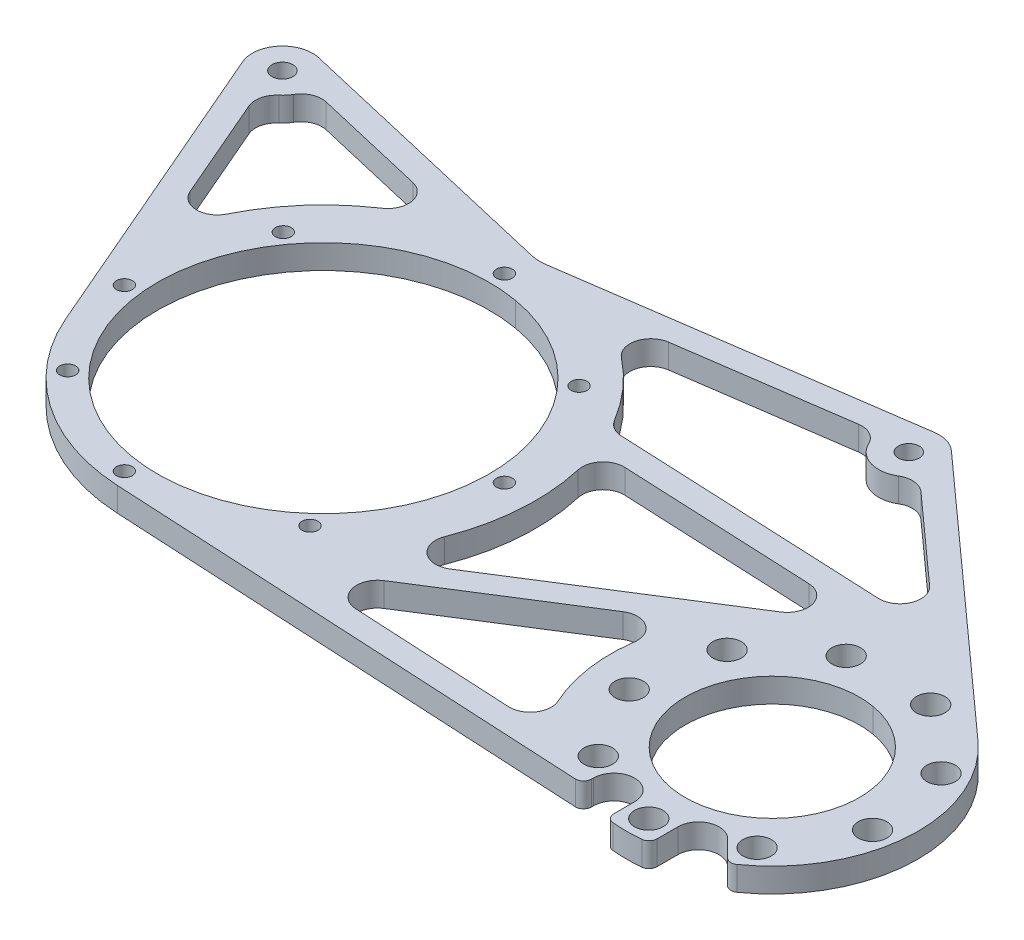
SolidWorks part; units mm, degrees
material "6061-T6 (SS)"
ref_plane "X-Y Datum" through (0, 0, 0) normal (0, 0, 1) x (1, 0, 0)
ref_plane "X-Z Datum" through (0, 0, 0) normal (0, 1, 0) x (1, 0, 0)
ref_plane "Y-Z Datum" through (0, 0, 0) normal (1, 0, 0) x (0, 0, -1)
sketch "Sketch2" plane through (0, 31.3819, 0) normal (0, 1, 0) x (1, 0, 0)
  line L0 (-693.7583, -176.702) -> (-693.7583, -183.2747) construction
  line L1 (-680.0808, -183.2747) -> (-680.0808, -176.702) construction
  line L2 (-668.9846, -172.1058) -> (-663.7197, -177.3707) construction
  line L3 (-693.7583, -176.702) -> (-693.7583, -183.2747)
  line L4 (-680.0808, -183.2747) -> (-680.0808, -176.702)
  line L5 (-668.9846, -172.1058) -> (-663.7197, -177.3707)
  line L6 (-966.641, -0.354) -> (-738.041, -0.354)
  line L7 (-727.7656, -5.5904) -> (-649.7224, -113.0358)
  line L9 (-977.8288, -19.0644) -> (-913.2312, -139.3061)
  line L10 (-706.7583, -177.279) -> (-706.7583, -176.702) construction
  line L11 (-706.7583, -177.279) -> (-706.7583, -176.702)
  line L12 (-861.9259, -171.8334) -> (-709.2983, -179.819)
  line L13 (-858.691, -110.0055) -> (-686.9195, -140.054) construction
  line L14 (-972.26, -24.9963) -> (-955.4664, -39.59) construction
  line L15 (-941.4162, -26.937) -> (-954.1775, -8.712) construction
  line L16 (-751.1929, -14.159) -> (-755.4346, -35.9995) construction
  line L17 (-737.4517, -41.8408) -> (-728.049, -21.6768) construction
  line L18 (-972.26, -24.9963) -> (-955.4664, -39.59)
  line L19 (-941.4162, -26.937) -> (-954.1775, -8.712)
  line L20 (-751.1929, -14.159) -> (-755.4346, -35.9995)
  line L21 (-737.4517, -41.8408) -> (-728.049, -21.6768)
  line L22 (-949.2186, -22.8753) -> (-746.0843, -28.2904)
  line L23 (-739.7146, -30.7335) -> (-656.1751, -105.8723)
  line L24 (-957.9647, -36.1729) -> (-915.5404, -134.527)
  arc A0 (-710.607, -179.4559) -> (-706.7583, -177.279) centre (-709.2983, -177.279) ccw construction
  arc A1 (-693.7583, -176.702) -> (-706.7583, -176.702) centre (-700.2583, -176.702) ccw construction
  arc A2 (-693.7583, -183.2747) -> (-691.4697, -185.8023) centre (-691.2183, -183.2747) ccw construction
  arc A3 (-691.4697, -185.8023) -> (-682.3694, -185.8023) centre (-686.9195, -140.054) ccw construction
  arc A4 (-682.3694, -185.8023) -> (-680.0808, -183.2747) centre (-682.6208, -183.2747) ccw construction
  arc A5 (-668.9846, -172.1058) -> (-680.0808, -176.702) centre (-673.5808, -176.702) ccw construction
  arc A6 (-663.7197, -177.3707) -> (-660.4619, -177.6519) centre (-661.9236, -175.5746) ccw construction
  arc A7 (-660.4619, -177.6519) -> (-710.607, -179.4559) centre (-686.9195, -140.054) ccw construction
  circle A8 centre (-858.691, -110.0055) radius 52.3875 construction
  circle A9 centre (-858.691, -110.0055) radius 61.9125 construction
  circle A10 centre (-738.041, -13.054) radius 12.7 construction
  circle A11 centre (-966.641, -13.054) radius 12.7 construction
  arc A12 (-710.607, -179.4559) -> (-706.7583, -177.279) centre (-709.2983, -177.279) ccw
  arc A13 (-693.7583, -176.702) -> (-706.7583, -176.702) centre (-700.2583, -176.702) ccw
  arc A14 (-693.7583, -183.2747) -> (-691.4697, -185.8023) centre (-691.2183, -183.2747) ccw
  arc A15 (-691.4697, -185.8023) -> (-682.3694, -185.8023) centre (-686.9195, -140.054) ccw
  arc A16 (-682.3694, -185.8023) -> (-680.0808, -183.2747) centre (-682.6208, -183.2747) ccw
  arc A17 (-668.9846, -172.1058) -> (-680.0808, -176.702) centre (-673.5808, -176.702) ccw
  arc A18 (-663.7197, -177.3707) -> (-660.4619, -177.6519) centre (-661.9236, -175.5746) ccw
  arc A19 (-660.4619, -177.6519) -> (-710.607, -179.4559) centre (-686.9195, -140.054) ccw
  circle A20 centre (-858.691, -110.0055) radius 52.3875
  circle A21 centre (-858.691, -110.0055) radius 61.9125
  circle A22 centre (-738.041, -13.054) radius 12.7
  circle A23 centre (-966.641, -13.054) radius 12.7
  circle A24 centre (-901.1618, -148.2463) radius 2.5 construction
  circle A25 centre (-915.528, -115.9793) radius 2.5 construction
  circle A26 centre (-904.9264, -76.4135) radius 2.5 construction
  circle A27 centre (-858.691, -52.8555) radius 2.5 construction
  circle A28 centre (-816.2203, -71.7646) radius 2.5 construction
  circle A29 centre (-801.541, -110.0055) radius 2.5 construction
  circle A30 centre (-820.4502, -152.4762) radius 2.5 construction
  circle A31 centre (-864.6648, -166.8424) radius 2.5 construction
  circle A32 centre (-901.1618, -148.2463) radius 2.5
  circle A33 centre (-915.528, -115.9793) radius 2.5
  circle A34 centre (-904.9264, -76.4135) radius 2.5
  circle A35 centre (-858.691, -52.8555) radius 2.5
  circle A36 centre (-816.2203, -71.7646) radius 2.5
  circle A37 centre (-801.541, -110.0055) radius 2.5
  circle A38 centre (-820.4502, -152.4762) radius 2.5
  circle A39 centre (-864.6648, -166.8424) radius 2.5
  circle A40 centre (-686.9195, -140.054) radius 27.4955 construction
  circle A41 centre (-686.9195, -140.054) radius 27.4955
  circle A42 centre (-711.9883, -169.9297) radius 4.5 construction
  circle A43 centre (-725.3271, -146.8263) radius 4.5 construction
  circle A44 centre (-720.6945, -120.554) radius 4.5 construction
  circle A45 centre (-700.2583, -103.406) radius 4.5 construction
  circle A46 centre (-673.5808, -103.406) radius 4.5 construction
  circle A47 centre (-653.1446, -120.554) radius 4.5 construction
  circle A48 centre (-648.512, -146.8263) radius 4.5 construction
  circle A49 centre (-661.8508, -169.9297) radius 4.5 construction
  circle A50 centre (-686.9195, -179.054) radius 4.5 construction
  circle A51 centre (-711.9883, -169.9297) radius 4.5
  circle A52 centre (-725.3271, -146.8263) radius 4.5
  circle A53 centre (-720.6945, -120.554) radius 4.5
  circle A54 centre (-700.2583, -103.406) radius 4.5
  circle A55 centre (-673.5808, -103.406) radius 4.5
  circle A56 centre (-653.1446, -120.554) radius 4.5
  circle A57 centre (-648.512, -146.8263) radius 4.5
  circle A58 centre (-661.8508, -169.9297) radius 4.5
  circle A59 centre (-686.9195, -179.054) radius 4.5
  circle A60 centre (-966.641, -13.054) radius 3.3
  circle A61 centre (-738.041, -13.054) radius 3.3
  arc A62 (-955.4664, -39.59) -> (-941.4162, -26.937) centre (-949.2186, -32.4003) ccw construction
  arc A63 (-749.3237, -37.1863) -> (-742.8448, -38.4445) centre (-746.0843, -37.8154) ccw construction
  arc A64 (-742.8448, -38.4445) -> (-749.3237, -37.1863) centre (-746.0843, -37.8154) ccw construction
  arc A65 (-755.4346, -35.9995) -> (-737.4517, -41.8408) centre (-746.0843, -37.8154) ccw construction
  arc A66 (-955.4664, -39.59) -> (-941.4162, -26.937) centre (-949.2186, -32.4003) ccw
  arc A67 (-749.3237, -37.1863) -> (-742.8448, -38.4445) centre (-746.0843, -37.8154) ccw
  arc A68 (-742.8448, -38.4445) -> (-749.3237, -37.1863) centre (-746.0843, -37.8154) ccw
  arc A69 (-755.4346, -35.9995) -> (-737.4517, -41.8408) centre (-746.0843, -37.8154) ccw
  circle A70 centre (-949.2186, -32.4003) radius 3.3
  circle A71 centre (-949.2186, -32.4003) radius 9.525
  circle A72 centre (-746.0843, -37.8154) radius 9.525
  point P94 (-949.2186, -32.4003)
  dimension "D1" = 6.6
  dimension "D2" = 6.6
  dimension "D3" = 6.6
extrude "Boss-Extrude1" add sketch "Sketch2" along normal blind 7.62 contours A21 A39 A38 A37 A36 A35 A34 A33 A32 A20 | A18 A19 A12 L11 A13 L3 A14 A15 A16 L4 A17 L5 A59 A58 A57 A56 A55 A54 A53 A52 A51 A41 | L13 A21 L12 A12 A19 | A21 L13 A19 L23 L21 A69 L20 L22 L19 A66 L18 L24 | A69 A72 A68 A67 | A72 L22 L20 | A72 L21 L23 | A71 L24 L18 | A71 L19 L22 | A71 A66 L22 A70 region at (-700.2583, 31.3819, 168.9016) region at (-773.051, 31.3819, 154.3682) region at (-890.9045, 31.3819, 160.8157) region at (-806.8861, 31.3819, 67.2042) region at (-956.9478, 31.3819, 38.0512) region at (-736.2382, 31.3819, 35.8095) region at (-956.6903, 31.3819, 37.8629) region at (-748.9437, 31.3819, 46.6182) region at (-752.4763, 31.3819, 29.8585) region at (-944.5842, 31.3819, 23.8004)
sketch "Sketch3" plane through (0, 31.3819, 0) normal (0, -1, 0) x (1, 0, 0)
  line L1 (-949.2186, 22.8753) -> (-746.0843, 28.2904) construction
  line L5 (-861.9259, 171.8334) -> (-709.2983, 179.819) construction
  line L6 (-977.8288, 19.0644) -> (-913.2312, 139.3061) construction
  line L7 (-727.7656, 5.5904) -> (-649.7224, 113.0358) construction
  line L13 (-751.1929, 14.159) -> (-755.4346, 35.9995) construction
  line L16 (-966.641, 0.354) -> (-738.041, 0.354) construction
  line L19 (-663.7197, 177.3707) -> (-668.9846, 172.1058)
  line L20 (-680.0808, 176.702) -> (-680.0808, 183.2747)
  line L21 (-693.7583, 183.2747) -> (-693.7583, 176.702)
  line L22 (-706.7583, 176.702) -> (-706.7583, 177.279)
  line L23 (-663.7197, 177.3707) -> (-668.9846, 172.1058)
  line L24 (-680.0808, 176.702) -> (-680.0808, 183.2747)
  line L25 (-693.7583, 183.2747) -> (-693.7583, 176.702)
  line L26 (-706.7583, 176.702) -> (-706.7583, 177.279)
  line L28 (-861.9259, 171.8334) -> (-709.2983, 179.819)
  line L29 (-977.8288, 19.0644) -> (-913.2312, 139.3061)
  line L30 (-727.7656, 5.5904) -> (-649.7224, 113.0358)
  line L31 (-966.641, 0.354) -> (-738.041, 0.354)
  line L34 (-737.4517, 41.8408) -> (-728.049, 21.6768) construction
  line L35 (-972.26, 24.9963) -> (-955.4664, 39.59) construction
  line L36 (-947.0539, 23.1246) -> (-856.9722, 44.1471)
  line L37 (-856.9722, 44.1471) -> (-747.4408, 28.3875)
  line L44 (-941.4162, 26.937) -> (-954.1775, 8.712) construction
  line L45 (-957.9647, 36.1729) -> (-915.5404, 134.527) construction
  line L46 (-739.7146, 30.7335) -> (-656.1751, 105.8723) construction
  line L47 (-861.9259, 171.8334) -> (-709.2983, 179.819)
  line L48 (-977.8288, 19.0644) -> (-913.2312, 139.3061)
  line L49 (-727.7656, 5.5904) -> (-649.7224, 113.0358)
  line L50 (-966.641, 0.354) -> (-738.041, 0.354)
  line L51 (-949.2186, 22.8753) -> (-746.0843, 28.2904)
  line L52 (-751.1929, 14.159) -> (-755.4346, 35.9995)
  line L53 (-737.4517, 41.8408) -> (-728.049, 21.6768)
  line L54 (-972.26, 24.9963) -> (-955.4664, 39.59)
  line L55 (-941.4162, 26.937) -> (-954.1775, 8.712)
  line L56 (-957.9647, 36.1729) -> (-915.5404, 134.527)
  line L57 (-739.7146, 30.7335) -> (-656.1751, 105.8723)
  arc A1 (-737.4517, 41.8408) -> (-755.4346, 35.9995) centre (-746.0843, 37.8154) ccw construction
  circle A3 centre (-966.641, 13.054) radius 12.7
  circle A5 centre (-966.641, 13.054) radius 12.7
  circle A7 centre (-738.041, 13.054) radius 12.7
  circle A9 centre (-738.041, 13.054) radius 12.7
  circle A11 centre (-858.691, 110.0055) radius 61.9125
  circle A13 centre (-858.691, 110.0055) radius 61.9125
  circle A15 centre (-858.691, 110.0055) radius 52.3875
  circle A17 centre (-858.691, 110.0055) radius 52.3875
  circle A19 centre (-686.9195, 140.054) radius 27.4955
  circle A21 centre (-686.9195, 140.054) radius 27.4955
  circle A23 centre (-864.6648, 166.8424) radius 2.5
  circle A25 centre (-864.6648, 166.8424) radius 2.5
  circle A27 centre (-820.4502, 152.4762) radius 2.5
  circle A29 centre (-820.4502, 152.4762) radius 2.5
  circle A31 centre (-801.541, 110.0055) radius 2.5
  circle A33 centre (-801.541, 110.0055) radius 2.5
  circle A35 centre (-816.2203, 71.7646) radius 2.5
  circle A37 centre (-816.2203, 71.7646) radius 2.5
  circle A39 centre (-858.691, 52.8555) radius 2.5
  circle A41 centre (-858.691, 52.8555) radius 2.5
  circle A43 centre (-904.9264, 76.4135) radius 2.5
  circle A46 centre (-904.9264, 76.4135) radius 2.5
  circle A47 centre (-915.528, 115.9793) radius 2.5
  circle A48 centre (-915.528, 115.9793) radius 2.5
  circle A49 centre (-901.1618, 148.2463) radius 2.5
  circle A50 centre (-901.1618, 148.2463) radius 2.5
  circle A51 centre (-720.6945, 120.554) radius 4.5
  circle A52 centre (-720.6945, 120.554) radius 4.5
  circle A68 centre (-725.3271, 146.8263) radius 4.5
  circle A69 centre (-725.3271, 146.8263) radius 4.5
  circle A70 centre (-711.9883, 169.9297) radius 4.5
  circle A71 centre (-711.9883, 169.9297) radius 4.5
  circle A72 centre (-738.041, 13.054) radius 3.3
  circle A73 centre (-738.041, 13.054) radius 3.3
  circle A74 centre (-966.641, 13.054) radius 3.3
  circle A75 centre (-966.641, 13.054) radius 3.3
  circle A76 centre (-686.9195, 179.054) radius 4.5
  circle A77 centre (-686.9195, 179.054) radius 4.5
  circle A78 centre (-661.8508, 169.9297) radius 4.5
  circle A79 centre (-661.8508, 169.9297) radius 4.5
  circle A80 centre (-648.512, 146.8263) radius 4.5
  circle A81 centre (-648.512, 146.8263) radius 4.5
  circle A82 centre (-653.1446, 120.554) radius 4.5
  circle A83 centre (-653.1446, 120.554) radius 4.5
  circle A84 centre (-673.5808, 103.406) radius 4.5
  circle A85 centre (-673.5808, 103.406) radius 4.5
  circle A86 centre (-700.2583, 103.406) radius 4.5
  circle A87 centre (-700.2583, 103.406) radius 4.5
  arc A95 (-710.607, 179.4559) -> (-660.4619, 177.6519) centre (-686.9195, 140.054) ccw
  arc A96 (-660.4619, 177.6519) -> (-663.7197, 177.3707) centre (-661.9236, 175.5746) ccw
  arc A97 (-680.0808, 176.702) -> (-668.9846, 172.1058) centre (-673.5808, 176.702) ccw
  arc A98 (-680.0808, 183.2747) -> (-682.3694, 185.8023) centre (-682.6208, 183.2747) ccw
  arc A99 (-682.3694, 185.8023) -> (-691.4697, 185.8023) centre (-686.9195, 140.054) ccw
  arc A100 (-691.4697, 185.8023) -> (-693.7583, 183.2747) centre (-691.2183, 183.2747) ccw
  arc A101 (-706.7583, 176.702) -> (-693.7583, 176.702) centre (-700.2583, 176.702) ccw
  arc A102 (-706.7583, 177.279) -> (-710.607, 179.4559) centre (-709.2983, 177.279) ccw
  arc A103 (-710.607, 179.4559) -> (-660.4619, 177.6519) centre (-686.9195, 140.054) ccw
  arc A104 (-660.4619, 177.6519) -> (-663.7197, 177.3707) centre (-661.9236, 175.5746) ccw
  arc A105 (-680.0808, 176.702) -> (-668.9846, 172.1058) centre (-673.5808, 176.702) ccw
  arc A106 (-680.0808, 183.2747) -> (-682.3694, 185.8023) centre (-682.6208, 183.2747) ccw
  arc A107 (-682.3694, 185.8023) -> (-691.4697, 185.8023) centre (-686.9195, 140.054) ccw
  arc A108 (-691.4697, 185.8023) -> (-693.7583, 183.2747) centre (-691.2183, 183.2747) ccw
  arc A109 (-706.7583, 176.702) -> (-693.7583, 176.702) centre (-700.2583, 176.702) ccw
  arc A110 (-706.7583, 177.279) -> (-710.607, 179.4559) centre (-709.2983, 177.279) ccw
  circle A152 centre (-746.0843, 37.8154) radius 9.525
  circle A153 centre (-746.0843, 37.8154) radius 9.525
  circle A154 centre (-949.2186, 32.4003) radius 9.525
  circle A155 centre (-949.2186, 32.4003) radius 9.525
  circle A156 centre (-949.2186, 32.4003) radius 3.3
  circle A157 centre (-949.2186, 32.4003) radius 3.3
  arc A158 (-941.4162, 26.937) -> (-955.4664, 39.59) centre (-949.2186, 32.4003) ccw construction
  arc A159 (-742.8448, 38.4445) -> (-749.3237, 37.1863) centre (-746.0843, 37.8154) ccw
  arc A160 (-749.3237, 37.1863) -> (-742.8448, 38.4445) centre (-746.0843, 37.8154) ccw
  arc A161 (-742.8448, 38.4445) -> (-749.3237, 37.1863) centre (-746.0843, 37.8154) ccw
  arc A162 (-749.3237, 37.1863) -> (-742.8448, 38.4445) centre (-746.0843, 37.8154) ccw
  arc A163 (-737.4517, 41.8408) -> (-755.4346, 35.9995) centre (-746.0843, 37.8154) ccw
  arc A164 (-941.4162, 26.937) -> (-955.4664, 39.59) centre (-949.2186, 32.4003) ccw
  dimension "D24" = 0
  dimension "D25" = 0
  dimension "D26" = 90.0818
  dimension "D27" = 21.0225
  dimension "D1" = 0
  dimension "D2" = 0
  dimension "D3" = 0
  dimension "D4" = 0
  dimension "D5" = 0
  dimension "D6" = 0
  dimension "D7" = 0
  dimension "D8" = 0
  dimension "D9" = 0
  dimension "D10" = 0
  dimension "D11" = 0
  dimension "D12" = 0
  dimension "D13" = 0
  dimension "D14" = 0
  dimension "D15" = 0
  dimension "D16" = 0
  dimension "D17" = 0
  dimension "D18" = 0
  dimension "D19" = 0
  dimension "D20" = 0
  dimension "D21" = 0
  dimension "D22" = 0
  dimension "D23" = 0
  dimension "D52" = 0
  dimension "D53" = 0
  dimension "D54" = 0
  dimension "D55" = 0
ref_point "Point1"
ref_point "Point2"
ref_plane "Plane1" through (-858.691, 31.3819, 110.0055) normal (0.985, 0, 0.1723) x (0.1723, 0, -0.985)
ref_plane "Plane2" through (-686.9195, 31.3819, 140.054) normal (-0.985, 0, -0.1723) x (-0.1723, 0, 0.985)
split line "Split Line1"
split line "Split Line2"
ref_axis "Axis1" through (-858.691, 39.0019, 110.0055) along (0, -1, 0)
ref_axis "Axis2" through (-686.9195, 39.0019, 140.054) along (0, -1, 0)
extrude "Cut-Extrude1" cut sketch "Sketch3" against normal through all contours L36 L55 L51 L52 L37 | A155 L51 L55 L36 | A153 L37 L52 L51 region at (-751.5495, 31.3819, 28.5688) region at (-850.6911, 31.3819, 31.7926) region at (-945.2616, 31.3819, 23.2848)
fillet "Fillet2" radius 12.7 1 edges at (-856.9722, 35.1919, 44.1471)
sketch "Sketch4" plane through (0, 31.3819, 0) normal (0, -1, 0) x (1, 0, 0)
  line L0 (-861.9259, 171.8334) -> (-709.2983, 179.819) construction
  line L1 (-727.7656, 5.5904) -> (-649.7224, 113.0358) construction
  line L2 (-977.8288, 19.0644) -> (-913.2312, 139.3061) construction
  line L4 (-706.7583, 176.702) -> (-706.7583, 177.279)
  line L5 (-663.7197, 177.3707) -> (-668.9846, 172.1058)
  line L6 (-680.0808, 176.702) -> (-680.0808, 183.2747)
  line L7 (-693.7583, 183.2747) -> (-693.7583, 176.702)
  line L8 (-706.7583, 176.702) -> (-706.7583, 177.279)
  line L9 (-663.7197, 177.3707) -> (-668.9846, 172.1058)
  line L10 (-680.0808, 176.702) -> (-680.0808, 183.2747)
  line L11 (-693.7583, 183.2747) -> (-693.7583, 176.702)
  line L13 (-966.641, 0.354) -> (-738.041, 0.354) construction
  line L14 (-861.9259, 171.8334) -> (-709.2983, 179.819)
  line L15 (-727.7656, 5.5904) -> (-649.7224, 113.0358)
  line L16 (-977.8288, 19.0644) -> (-913.2312, 139.3061)
  line L17 (-861.9259, 171.8334) -> (-709.2983, 179.819) construction
  line L19 (-966.641, 0.354) -> (-738.041, 0.354)
  line L20 (-924.088, 95.4716) -> (-952.4637, 29.6868)
  line L21 (-952.4637, 29.6868) -> (-880.185, 46.5546)
  line L22 (-727.338, 171.2447) -> (-811.2904, 166.8523)
  line L23 (-811.2904, 166.8523) -> (-732.4764, 117.0088)
  line L24 (-812.7344, 158.7495) -> (-704.8294, 90.5083)
  line L25 (-704.8294, 90.5083) -> (-795.9976, 86.3933)
  line L26 (-832.536, 48.3296) -> (-755.593, 37.2589)
  line L27 (-799.5123, 78.6069) -> (-692.5141, 83.4364)
  line L28 (-692.5141, 83.4364) -> (-737.8716, 42.64)
  line L29 (-977.8288, 19.0644) -> (-913.2312, 139.3061) construction
  line L30 (-727.7656, 5.5904) -> (-649.7224, 113.0358) construction
  line L31 (-966.641, 0.354) -> (-738.041, 0.354) construction
  line L32 (-663.7197, 177.3707) -> (-668.9846, 172.1058)
  line L33 (-680.0808, 176.702) -> (-680.0808, 183.2747)
  line L34 (-693.7583, 183.2747) -> (-693.7583, 176.702)
  line L35 (-706.7583, 176.702) -> (-706.7583, 177.279)
  line L36 (-663.7197, 177.3707) -> (-668.9846, 172.1058)
  line L37 (-680.0808, 176.702) -> (-680.0808, 183.2747)
  line L38 (-693.7583, 183.2747) -> (-693.7583, 176.702)
  line L39 (-706.7583, 176.702) -> (-706.7583, 177.279)
  line L40 (-949.2186, 22.8753) -> (-746.0843, 28.2904) construction
  line L41 (-751.1929, 14.159) -> (-755.4346, 35.9995) construction
  line L42 (-737.4517, 41.8408) -> (-728.049, 21.6768) construction
  line L43 (-972.26, 24.9963) -> (-955.4664, 39.59) construction
  line L44 (-941.4162, 26.937) -> (-954.1775, 8.712) construction
  line L45 (-957.9647, 36.1729) -> (-915.5404, 134.527) construction
  line L46 (-739.7146, 30.7335) -> (-656.1751, 105.8723) construction
  line L47 (-861.9259, 171.8334) -> (-709.2983, 179.819)
  line L48 (-977.8288, 19.0644) -> (-913.2312, 139.3061)
  line L49 (-727.7656, 5.5904) -> (-649.7224, 113.0358)
  line L50 (-966.641, 0.354) -> (-738.041, 0.354)
  line L51 (-949.2186, 22.8753) -> (-746.0843, 28.2904)
  line L52 (-751.1929, 14.159) -> (-755.4346, 35.9995)
  line L53 (-737.4517, 41.8408) -> (-728.049, 21.6768)
  line L54 (-972.26, 24.9963) -> (-955.4664, 39.59)
  line L55 (-941.4162, 26.937) -> (-954.1775, 8.712)
  line L56 (-957.9647, 36.1729) -> (-915.5404, 134.527)
  line L57 (-739.7146, 30.7335) -> (-656.1751, 105.8723)
  line L58 (-947.0539, 23.1246) -> (-859.3005, 43.6037) construction
  line L60 (-854.6056, 43.8066) -> (-747.4408, 28.3875) construction
  circle A1 centre (-858.691, 110.0055) radius 52.3875
  circle A2 centre (-858.691, 110.0055) radius 52.3875
  circle A3 centre (-858.691, 110.0055) radius 61.9125
  circle A4 centre (-858.691, 110.0055) radius 61.9125
  circle A5 centre (-738.041, 13.054) radius 12.7
  circle A6 centre (-738.041, 13.054) radius 12.7
  circle A7 centre (-966.641, 13.054) radius 12.7
  circle A8 centre (-966.641, 13.054) radius 12.7
  circle A9 centre (-858.691, 52.8555) radius 2.5
  circle A10 centre (-858.691, 52.8555) radius 2.5
  circle A11 centre (-816.2203, 71.7646) radius 2.5
  circle A12 centre (-816.2203, 71.7646) radius 2.5
  circle A13 centre (-801.541, 110.0055) radius 2.5
  circle A14 centre (-801.541, 110.0055) radius 2.5
  circle A15 centre (-820.4502, 152.4762) radius 2.5
  circle A16 centre (-820.4502, 152.4762) radius 2.5
  circle A17 centre (-864.6648, 166.8424) radius 2.5
  circle A18 centre (-864.6648, 166.8424) radius 2.5
  circle A19 centre (-686.9195, 140.054) radius 27.4955
  circle A20 centre (-686.9195, 140.054) radius 27.4955
  circle A21 centre (-725.3271, 146.8263) radius 4.5
  circle A22 centre (-725.3271, 146.8263) radius 4.5
  circle A23 centre (-720.6945, 120.554) radius 4.5
  circle A24 centre (-720.6945, 120.554) radius 4.5
  circle A25 centre (-901.1618, 148.2463) radius 2.5
  circle A26 centre (-901.1618, 148.2463) radius 2.5
  circle A27 centre (-915.528, 115.9793) radius 2.5
  circle A28 centre (-915.528, 115.9793) radius 2.5
  circle A29 centre (-904.9264, 76.4135) radius 2.5
  circle A30 centre (-904.9264, 76.4135) radius 2.5
  circle A31 centre (-661.8508, 169.9297) radius 4.5
  circle A32 centre (-661.8508, 169.9297) radius 4.5
  circle A33 centre (-686.9195, 179.054) radius 4.5
  circle A34 centre (-686.9195, 179.054) radius 4.5
  circle A35 centre (-966.641, 13.054) radius 3.3
  circle A36 centre (-966.641, 13.054) radius 3.3
  circle A37 centre (-738.041, 13.054) radius 3.3
  circle A38 centre (-738.041, 13.054) radius 3.3
  circle A39 centre (-711.9883, 169.9297) radius 4.5
  circle A40 centre (-711.9883, 169.9297) radius 4.5
  circle A41 centre (-700.2583, 103.406) radius 4.5
  circle A42 centre (-700.2583, 103.406) radius 4.5
  circle A43 centre (-673.5808, 103.406) radius 4.5
  circle A44 centre (-673.5808, 103.406) radius 4.5
  circle A45 centre (-653.1446, 120.554) radius 4.5
  circle A46 centre (-653.1446, 120.554) radius 4.5
  circle A47 centre (-648.512, 146.8263) radius 4.5
  circle A48 centre (-648.512, 146.8263) radius 4.5
  arc A49 (-880.185, 46.5546) -> (-924.088, 95.4716) centre (-858.691, 110.0055) cw
  arc A50 (-727.338, 171.2447) -> (-732.4764, 117.0088) centre (-686.9195, 140.054) ccw
  arc A51 (-812.7344, 158.7495) -> (-795.9976, 86.3933) centre (-858.691, 110.0055) cw
  arc A52 (-832.536, 48.3296) -> (-799.5123, 78.6069) centre (-858.691, 110.0055) ccw
  arc A53 (-737.4517, 41.8408) -> (-755.4346, 35.9995) centre (-746.0843, 37.8154) ccw construction
  circle A54 centre (-966.641, 13.054) radius 12.7
  circle A55 centre (-966.641, 13.054) radius 12.7
  arc A56 (-706.7583, 177.279) -> (-710.607, 179.4559) centre (-709.2983, 177.279) ccw
  arc A57 (-710.607, 179.4559) -> (-660.4619, 177.6519) centre (-686.9195, 140.054) ccw
  arc A58 (-660.4619, 177.6519) -> (-663.7197, 177.3707) centre (-661.9236, 175.5746) ccw
  arc A59 (-680.0808, 176.702) -> (-668.9846, 172.1058) centre (-673.5808, 176.702) ccw
  arc A60 (-680.0808, 183.2747) -> (-682.3694, 185.8023) centre (-682.6208, 183.2747) ccw
  arc A61 (-682.3694, 185.8023) -> (-691.4697, 185.8023) centre (-686.9195, 140.054) ccw
  arc A62 (-691.4697, 185.8023) -> (-693.7583, 183.2747) centre (-691.2183, 183.2747) ccw
  arc A63 (-706.7583, 176.702) -> (-693.7583, 176.702) centre (-700.2583, 176.702) ccw
  arc A64 (-706.7583, 177.279) -> (-710.607, 179.4559) centre (-709.2983, 177.279) ccw
  arc A65 (-710.607, 179.4559) -> (-660.4619, 177.6519) centre (-686.9195, 140.054) ccw
  arc A66 (-660.4619, 177.6519) -> (-663.7197, 177.3707) centre (-661.9236, 175.5746) ccw
  arc A67 (-680.0808, 176.702) -> (-668.9846, 172.1058) centre (-673.5808, 176.702) ccw
  arc A68 (-680.0808, 183.2747) -> (-682.3694, 185.8023) centre (-682.6208, 183.2747) ccw
  arc A69 (-682.3694, 185.8023) -> (-691.4697, 185.8023) centre (-686.9195, 140.054) ccw
  arc A70 (-691.4697, 185.8023) -> (-693.7583, 183.2747) centre (-691.2183, 183.2747) ccw
  arc A71 (-706.7583, 176.702) -> (-693.7583, 176.702) centre (-700.2583, 176.702) ccw
  circle A72 centre (-738.041, 13.054) radius 12.7
  circle A73 centre (-738.041, 13.054) radius 12.7
  circle A74 centre (-858.691, 110.0055) radius 61.9125
  circle A75 centre (-858.691, 110.0055) radius 61.9125
  circle A76 centre (-858.691, 110.0055) radius 52.3875
  circle A77 centre (-858.691, 110.0055) radius 52.3875
  circle A78 centre (-686.9195, 140.054) radius 27.4955
  circle A79 centre (-686.9195, 140.054) radius 27.4955
  circle A80 centre (-864.6648, 166.8424) radius 2.5
  circle A81 centre (-864.6648, 166.8424) radius 2.5
  circle A82 centre (-820.4502, 152.4762) radius 2.5
  circle A83 centre (-820.4502, 152.4762) radius 2.5
  circle A84 centre (-801.541, 110.0055) radius 2.5
  circle A85 centre (-801.541, 110.0055) radius 2.5
  circle A86 centre (-816.2203, 71.7646) radius 2.5
  circle A87 centre (-816.2203, 71.7646) radius 2.5
  circle A88 centre (-858.691, 52.8555) radius 2.5
  circle A89 centre (-858.691, 52.8555) radius 2.5
  circle A90 centre (-904.9264, 76.4135) radius 2.5
  circle A91 centre (-904.9264, 76.4135) radius 2.5
  circle A92 centre (-915.528, 115.9793) radius 2.5
  circle A93 centre (-915.528, 115.9793) radius 2.5
  circle A94 centre (-901.1618, 148.2463) radius 2.5
  circle A95 centre (-901.1618, 148.2463) radius 2.5
  circle A96 centre (-720.6945, 120.554) radius 4.5
  circle A97 centre (-720.6945, 120.554) radius 4.5
  circle A98 centre (-725.3271, 146.8263) radius 4.5
  circle A99 centre (-725.3271, 146.8263) radius 4.5
  circle A100 centre (-711.9883, 169.9297) radius 4.5
  circle A101 centre (-711.9883, 169.9297) radius 4.5
  circle A102 centre (-738.041, 13.054) radius 3.3
  circle A103 centre (-738.041, 13.054) radius 3.3
  circle A104 centre (-966.641, 13.054) radius 3.3
  circle A105 centre (-966.641, 13.054) radius 3.3
  circle A106 centre (-686.9195, 179.054) radius 4.5
  circle A107 centre (-686.9195, 179.054) radius 4.5
  circle A108 centre (-661.8508, 169.9297) radius 4.5
  circle A109 centre (-661.8508, 169.9297) radius 4.5
  circle A110 centre (-648.512, 146.8263) radius 4.5
  circle A111 centre (-648.512, 146.8263) radius 4.5
  circle A112 centre (-653.1446, 120.554) radius 4.5
  circle A113 centre (-653.1446, 120.554) radius 4.5
  circle A114 centre (-673.5808, 103.406) radius 4.5
  circle A115 centre (-673.5808, 103.406) radius 4.5
  circle A116 centre (-700.2583, 103.406) radius 4.5
  circle A117 centre (-700.2583, 103.406) radius 4.5
  circle A118 centre (-746.0843, 37.8154) radius 9.525
  circle A119 centre (-746.0843, 37.8154) radius 9.525
  circle A120 centre (-949.2186, 32.4003) radius 9.525
  circle A121 centre (-949.2186, 32.4003) radius 9.525
  circle A122 centre (-949.2186, 32.4003) radius 3.3
  circle A123 centre (-949.2186, 32.4003) radius 3.3
  arc A124 (-941.4162, 26.937) -> (-955.4664, 39.59) centre (-949.2186, 32.4003) ccw construction
  arc A125 (-742.8448, 38.4445) -> (-749.3237, 37.1863) centre (-746.0843, 37.8154) ccw
  arc A126 (-749.3237, 37.1863) -> (-742.8448, 38.4445) centre (-746.0843, 37.8154) ccw
  arc A127 (-742.8448, 38.4445) -> (-749.3237, 37.1863) centre (-746.0843, 37.8154) ccw
  arc A128 (-749.3237, 37.1863) -> (-742.8448, 38.4445) centre (-746.0843, 37.8154) ccw
  arc A129 (-737.4517, 41.8408) -> (-755.4346, 35.9995) centre (-746.0843, 37.8154) ccw
  arc A130 (-941.4162, 26.937) -> (-955.4664, 39.59) centre (-949.2186, 32.4003) ccw
  arc A135 (-710.607, 179.4559) -> (-660.4619, 177.6519) centre (-686.9195, 140.054) ccw
  arc A136 (-660.4619, 177.6519) -> (-663.7197, 177.3707) centre (-661.9236, 175.5746) ccw
  arc A137 (-680.0808, 176.702) -> (-668.9846, 172.1058) centre (-673.5808, 176.702) ccw
  arc A138 (-680.0808, 183.2747) -> (-682.3694, 185.8023) centre (-682.6208, 183.2747) ccw
  arc A139 (-682.3694, 185.8023) -> (-691.4697, 185.8023) centre (-686.9195, 140.054) ccw
  arc A140 (-691.4697, 185.8023) -> (-693.7583, 183.2747) centre (-691.2183, 183.2747) ccw
  arc A141 (-706.7583, 176.702) -> (-693.7583, 176.702) centre (-700.2583, 176.702) ccw
  arc A142 (-706.7583, 177.279) -> (-710.607, 179.4559) centre (-709.2983, 177.279) ccw
  arc A143 (-710.607, 179.4559) -> (-660.4619, 177.6519) centre (-686.9195, 140.054) ccw
  arc A144 (-660.4619, 177.6519) -> (-663.7197, 177.3707) centre (-661.9236, 175.5746) ccw
  arc A145 (-680.0808, 176.702) -> (-668.9846, 172.1058) centre (-673.5808, 176.702) ccw
  arc A146 (-680.0808, 183.2747) -> (-682.3694, 185.8023) centre (-682.6208, 183.2747) ccw
  arc A147 (-682.3694, 185.8023) -> (-691.4697, 185.8023) centre (-686.9195, 140.054) ccw
  arc A148 (-691.4697, 185.8023) -> (-693.7583, 183.2747) centre (-691.2183, 183.2747) ccw
  arc A149 (-706.7583, 176.702) -> (-693.7583, 176.702) centre (-700.2583, 176.702) ccw
  arc A150 (-706.7583, 177.279) -> (-710.607, 179.4559) centre (-709.2983, 177.279) ccw
  dimension "D26" = 5.08
  dimension "D29" = 5.08
  dimension "D30" = 5.08
  dimension "D35" = 0
  dimension "D39" = 5.08
  dimension "D27" = 0
  dimension "D28" = 0
  dimension "D31" = 7.62
  dimension "D32" = 7.62
  dimension "D33" = 93.2524
  dimension "D34" = 49.8435
  dimension "D36" = 91.1683
  dimension "D37" = 4.1149
  dimension "D38" = 7.62
  dimension "D40" = 7.62
  dimension "D67" = 7.62
  dimension "D68" = 7.62
  dimension "D69" = 7.62
  dimension "D1" = 0
  dimension "D2" = 0
  dimension "D3" = 0
  dimension "D4" = 0
  dimension "D5" = 0
  dimension "D6" = 0
  dimension "D7" = 0
  dimension "D8" = 0
  dimension "D9" = 0
  dimension "D10" = 0
  dimension "D11" = 0
  dimension "D12" = 0
  dimension "D13" = 0
  dimension "D14" = 0
  dimension "D15" = 0
  dimension "D16" = 0
  dimension "D17" = 0
  dimension "D18" = 0
  dimension "D19" = 0
  dimension "D20" = 0
  dimension "D21" = 0
  dimension "D22" = 0
  dimension "D23" = 0
  dimension "D24" = 0
  dimension "D25" = 0
  dimension "D41" = 0
  dimension "D42" = 0
  dimension "D43" = 0
  dimension "D44" = 0
  dimension "D45" = 0
  dimension "D46" = 0
  dimension "D47" = 0
  dimension "D48" = 0
  dimension "D49" = 0
  dimension "D50" = 0
  dimension "D51" = 0
  dimension "D52" = 0
  dimension "D53" = 0
  dimension "D54" = 0
  dimension "D55" = 0
  dimension "D56" = 0
  dimension "D57" = 0
  dimension "D58" = 0
  dimension "D59" = 0
  dimension "D60" = 0
  dimension "D61" = 0
  dimension "D62" = 0
  dimension "D63" = 0
  dimension "D64" = 0
  dimension "D65" = 0
  dimension "D66" = 0
extrude "Cut-Extrude2" cut sketch "Sketch4" against normal through all contours L21 A49 L20 A8 | A52 L26 A6 L28 L27 | L24 A51 L25 | A50 L22 L23 region at (-762.9009, 31.3819, 62.1515) region at (-920.7879, 31.3819, 55.7375) region at (-760.5637, 31.3819, 152.7731) region at (-765.2993, 31.3819, 109.4875)
fillet "Fillet3" radius 6.604 15 edges at (-732.4764, 35.1919, 117.0088) (-727.338, 35.1919, 171.2447) (-811.2904, 35.1919, 166.8523) (-704.8294, 35.1919, 90.5083) (-795.9976, 35.1919, 86.3933) (-812.7344, 35.1919, 158.7495) (-692.5141, 35.1919, 83.4364) (-799.5123, 35.1919, 78.6069) (-832.536, 35.1919, 48.3296) (-880.185, 35.1919, 46.5546) (-924.088, 35.1919, 95.4716) (-737.8716, 35.1919, 42.64) (-755.593, 35.1919, 37.2589) (-939.6973, 35.1919, 32.6661) (-947.2715, 35.1919, 41.7242)
split line "Split Line3"
sketch "Sketch2<4>" plane through (0, 31.3819, 0) normal (0, 1, 0) x (1, 0, 0) same geometry as "Sketch2"
